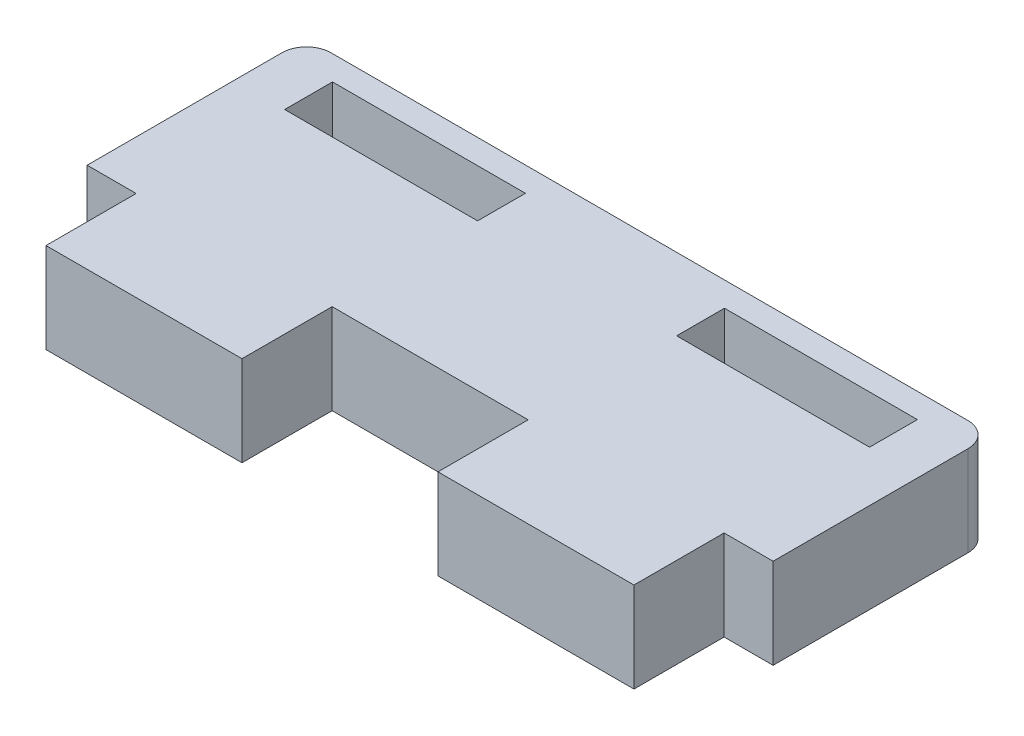
SolidWorks part; units mm, degrees
ref_plane "Front Plane" through (0, 0, 0) normal (0, 0, 1) x (1, 0, 0)
ref_plane "Top Plane" through (0, 0, 0) normal (0, 1, 0) x (1, 0, 0)
ref_plane "Right Plane" through (0, 0, 0) normal (1, 0, 0) x (0, 0, -1)
sketch "Sketch1" plane through (0, 0, 0) normal (0, 1, 0) x (1, 0, 0)
  line L0 (0, 4.7625) -> (0, -4.7625) construction
  line L1 (22.225, -4.7625) -> (19.05, -4.7625)
  line L2 (22.225, -4.7625) -> (22.225, 4.7625)
  line L3 (18.95, 4.7625) -> (6.45, 4.7625)
  line L4 (-22.225, -4.7625) -> (-22.225, 4.7625)
  line L5 (22.225, -4.7625) -> (-22.225, 4.7625) construction
  line L6 (22.225, 4.7625) -> (-22.225, -4.7625) construction
  line L7 (-6.35, -10.6045) -> (-19.05, -10.6045)
  line L8 (-6.35, -10.6045) -> (-6.35, -4.7625)
  line L9 (6.35, -4.7625) -> (-6.35, -4.7625)
  line L10 (-19.05, -10.6045) -> (-19.05, -4.7625)
  line L11 (-6.35, -10.6045) -> (-19.05, -4.7625) construction
  line L12 (-6.35, -4.7625) -> (-19.05, -10.6045) construction
  line L13 (-6.45, 7.8613) -> (-18.95, 7.8613)
  line L14 (6.45, 7.8613) -> (6.45, 4.7625)
  line L15 (6.35, -10.6045) -> (6.35, -4.7625)
  line L16 (-6.45, 7.8613) -> (-6.45, 4.7625)
  line L17 (6.45, 7.8613) -> (-6.45, 4.7625) construction
  line L18 (6.45, 4.7625) -> (-6.45, 7.8613) construction
  line L19 (18.95, 4.7625) -> (18.95, 7.8613)
  line L20 (-6.45, 4.7625) -> (-18.95, 4.7625)
  line L21 (-22.225, 4.7625) -> (-22.225, 7.8613)
  line L22 (19.05, -10.6045) -> (19.05, -4.7625)
  line L23 (-18.95, 4.7625) -> (-18.95, 7.8613)
  line L24 (6.35, -10.6045) -> (19.05, -10.6045)
  line L25 (22.225, 4.7625) -> (22.225, 7.8613)
  line L26 (22.225, 9.4488) -> (-22.225, 9.4488)
  line L27 (22.225, 9.4488) -> (22.225, 7.8613)
  line L28 (18.95, 7.8613) -> (6.45, 7.8613)
  line L29 (-22.225, 9.4488) -> (-22.225, 7.8613)
  line L30 (22.225, 9.4488) -> (-22.225, 7.8613) construction
  line L31 (22.225, 7.8613) -> (-22.225, 9.4488) construction
  line L32 (-19.05, -4.7625) -> (-22.225, -4.7625)
  point P0 (0, 0)
  point P6 (-12.7, -7.6835)
  point P11 (0, 6.3119)
  point P24 (0, 8.6551)
  dimension "D1" = 44.45
  dimension "D2" = 9.525
  dimension "D3" = 3.0988
  dimension "D4" = 12.9
  dimension "D5" = 3.0988
  dimension "D6" = 3.275
  dimension "D7" = 1.5875
  dimension "D8" = 5.842
  dimension "D9" = 12.7
  dimension "D10" = 12.7
extrude "Boss-Extrude1" add sketch "Sketch1" along normal blind 5.842
fillet "Fillet1" radius 1.5875 2 edges at (22.225, 2.921, -9.4488) (-22.225, 2.921, -9.4488)
